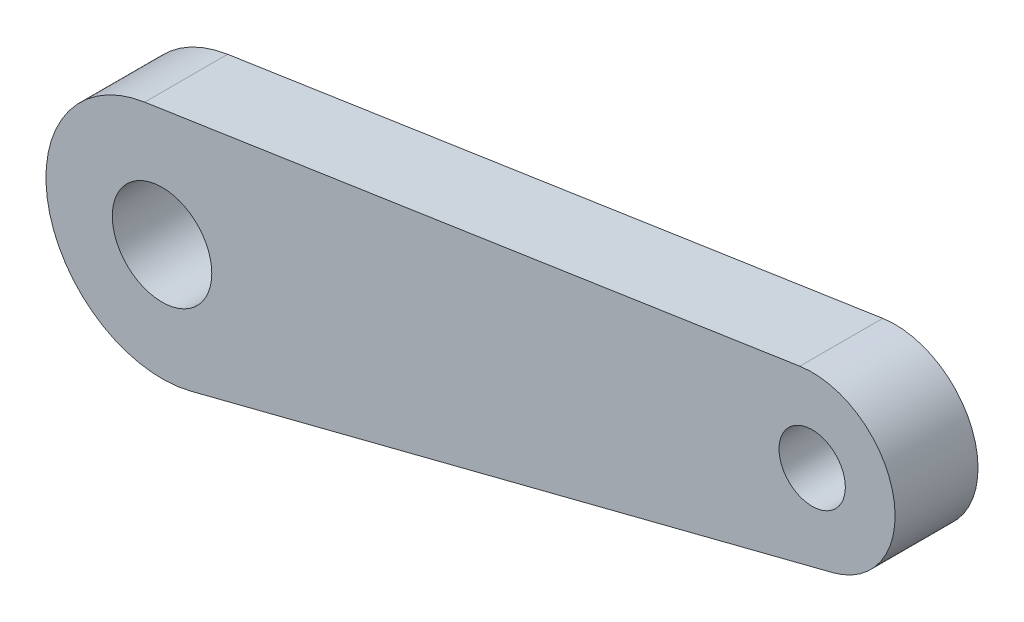
SolidWorks part; units mm, degrees
ref_plane "Front Plane" through (0, 0, 0) normal (0, 0, 1) x (1, 0, 0)
ref_plane "Top Plane" through (0, 0, 0) normal (0, 1, 0) x (1, 0, 0)
ref_plane "Right Plane" through (0, 0, 0) normal (1, 0, 0) x (0, 0, -1)
sketch "Sketch1" plane through (0, 0, 0) normal (0, 0, 1) x (1, 0, 0)
  line L0 (-51.0445, 24.9216) -> (-11.5418, 30.8829)
  line L1 (-9.5596, 21.0941) -> (-48.2694, 11.2173)
  circle A0 centre (-50, 18) radius 3 construction
  circle A1 centre (-10.7957, 25.9389) radius 2 construction
  circle A2 centre (-50, 18) radius 3
  circle A3 centre (-10.7957, 25.9389) radius 2
  arc A4 (-11.5418, 30.8829) -> (-9.5596, 21.0941) centre (-10.7957, 25.9389) cw
  arc A5 (-48.2694, 11.2173) -> (-51.0445, 24.9216) centre (-50, 18) cw
  dimension "D1" = 5
  dimension "D2" = 7
extrude "Boss-Extrude1" add sketch "Sketch1" along normal blind 5 from offset 10
